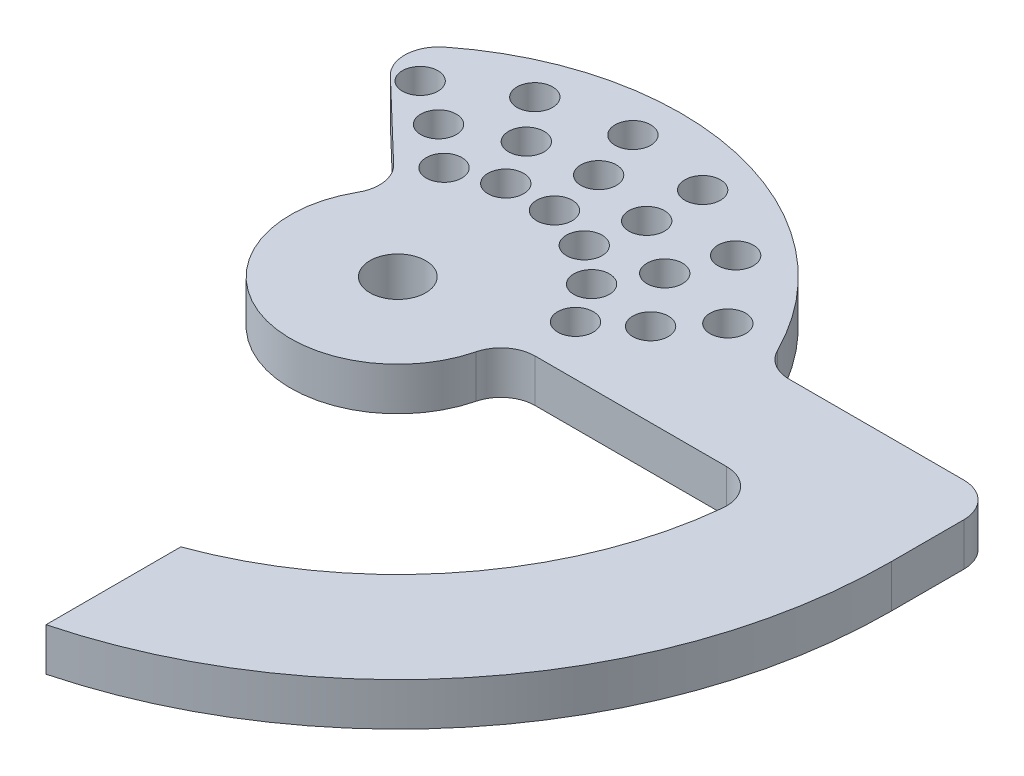
SolidWorks part; units mm, degrees
ref_plane "Front Plane" through (0, 0, 0) normal (0, 0, 1) x (1, 0, 0)
ref_plane "Top Plane" through (0, 0, 0) normal (0, 1, 0) x (1, 0, 0)
ref_plane "Right Plane" through (0, 0, 0) normal (1, 0, 0) x (0, 0, -1)
sketch "Sketch1" plane through (0, 0, 0) normal (0, 1, 0) x (1, 0, 0)
  circle A0 centre (0, 0) radius 12.5
  dimension "D1" = 25
extrude "Boss-Extrude1" add sketch "Sketch1" along normal blind 5
sketch "Sketch4" plane through (0, 0, 0) normal (0, 1, 0) x (1, 0, 0)
  line L0 (0, 0) -> (50, 0) construction
  line L1 (0, 0) -> (14.6186, -47.8152) construction
  arc A0 (14.6186, -47.8152) -> (50, 0) centre (0, 0) ccw
  dimension "D2" = 73
  dimension "D3" = 50
extrude "Extrude-Thin1" add sketch "Sketch4" along normal blind 5 separate body thin thin type mid plane wall 15
sketch "Sketch6" plane through (0, 0, 0) normal (0, 1, 0) x (1, 0, 0)
  line L1 (57.5, 0) -> (1, 0)
  line L2 (57.5, 0) -> (57.5, 12.4599)
  line L3 (57.5, 12.4599) -> (1, 12.4599)
  line L4 (1, 0) -> (1, 12.4599)
  line L5 (29.25, 12.4599) -> (29.25, 0) construction
  line L6 (57.5, 6.23) -> (1, 6.23) construction
  circle A0 centre (0, 0) radius 12.5 construction
  point P104 (29.25, 6.23)
extrude "Boss-Extrude3" add sketch "Sketch6" along normal up to surface (5 mm away) up to face at (0, 5, 12.5)
sketch "Sketch7" plane through (0, 5, 0) normal (0, 1, 0) x (1, 0, 0)
  circle A0 centre (0, 0) radius 3.25
  dimension "D1" = 6.5
extrude "Cut-Extrude3" cut sketch "Sketch7" against normal through all both and the other way through all
sketch "Sketch9" plane through (0, 0, 0) normal (0, 1, 0) x (1, 0, 0)
  line L0 (16.8114, -54.9875) -> (12.4258, -40.643) construction
  line L1 (0, 0) -> (23.9434, 0) construction
  line L2 (12.5, 0) -> (42.5, 0) construction
  line L3 (14.6186, 0) -> (14.6186, -61.8648) construction
  line L4 (12.4258, -40.643) -> (11.863, -56.263)
  line L5 (14.6186, -37.5897) -> (4.9921, -37.5897)
  line L6 (14.6186, -37.5897) -> (14.6186, -60.7122)
  line L7 (14.6186, -60.7122) -> (4.9921, -60.7122)
  line L8 (4.9921, -37.5897) -> (4.9921, -60.7122)
  line L9 (9.8053, -60.7122) -> (9.8053, -37.5897) construction
  line L10 (14.6186, -49.151) -> (4.9921, -49.151) construction
  line L11 (16.8114, -54.9875) -> (12.4258, -40.643)
  arc A0 (16.8114, -54.9875) -> (11.863, -56.263) centre (0, 0) cw
  point P0 (14.6186, -47.8152)
  point P166 (9.8053, -49.151)
extrude "Boss-Extrude4" add sketch "Sketch9" along normal blind 5 contours A0 L11 L6 | A0 L6 L11 L4 region at (13.2318, 0, 50.04) region at (15.3502, 0, 52.8095)
extrude "Cut-Extrude5" cut sketch "Sketch9<4>" along normal through all contours L6 L7 L8 L5
sketch "Sketch9<4>" plane through (0, 0, 0) normal (0, 1, 0) x (1, 0, 0) same geometry as "Sketch9"
sketch "Sketch10" plane through (0, 0, 0) normal (0, 1, 0) x (1, 0, 0)
  line L0 (0, 0) -> (-23.8274, 22.8311) construction
  line L4 (-23.8274, 22.8311) -> (-5.9312, 5.6832)
  line L6 (31.686, 9.2196) -> (0, 0) construction
  line L7 (31.686, 9.2196) -> (19.5321, 5.6832)
  line L8 (19.5321, 5.6832) -> (-5.9312, 5.6832)
  arc A0 (-23.8274, 22.8311) -> (31.686, 9.2196) centre (0, 0) cw
  point P5 (33.6063, 9.7783)
  point P7 (-24.9195, 24.5768)
  dimension "D1" = 33
  dimension "D2" = 120
extrude "Boss-Extrude5" add sketch "Sketch10" along normal up to surface (5 mm away) up to face at (28.5796, 5, 13.8571)
sketch "Sketch11" plane through (0, 5, 0) normal (0, 1, 0) x (1, 0, 0)
  line L0 (0, 0) -> (-17.1064, 28.2201) construction
  line L1 (-23.8274, 22.8311) -> (-9.0255, 8.6481) construction
  arc A0 (30.5573, 12.4599) -> (-23.8274, 22.8311) centre (0, 0) ccw construction
  circle A2 centre (-8.294, 13.6825) radius 2.075
  dimension "D2" = 4.15
  dimension "D4" = 16
  dimension "D5" = 15
extrude "Cut-Extrude6" cut sketch "Sketch11" against normal through all
sketch "Sketch12" plane through (0, 5, 0) normal (0, 1, 0) x (1, 0, 0)
  line L0 (0, 0) -> (-17.1064, 28.2201) construction
  line L1 (-23.8274, 22.8311) -> (-9.0255, 8.6481) construction
  line L2 (0, 0) -> (-19.5008, 26.6218) construction
  arc A0 (30.5573, 12.4599) -> (-23.8274, 22.8311) centre (0, 0) ccw construction
  circle A1 centre (-13.0005, 17.7478) radius 2.075
  point P11 (-9.4549, 12.9075)
  dimension "D3" = 6
  dimension "D4" = 4.15
  dimension "D1" = 15
  dimension "D2" = 16
  dimension "D5" = 5
extrude "Cut-Extrude7" cut sketch "Sketch12" against normal through all
sketch "Sketch13" plane through (0, 5, 0) normal (0, 1, 0) x (1, 0, 0)
  line L0 (0, 0) -> (-17.1064, 28.2201) construction
  line L1 (0, 0) -> (-21.7468, 24.8209) construction
  line L2 (-23.8274, 22.8311) -> (-9.0255, 8.6481) construction
  arc A0 (30.5573, 12.4599) -> (-23.8274, 22.8311) centre (0, 0) ccw construction
  circle A1 centre (-18.4519, 21.0601) radius 2.075
  point P9 (-14.4979, 16.5472)
  dimension "D3" = 4.15
  dimension "D5" = 6
  dimension "D1" = 15
  dimension "D2" = 10
  dimension "D4" = 22
extrude "Cut-Extrude8" cut sketch "Sketch13" against normal through all
pattern_circular "CirPattern1" count 6 every 20 about axis through (0, 5, 0) along (0, 1, 0) of "Cut-Extrude6" reverse direction yes
pattern_circular "CirPattern2" count 6 every 20 about axis through (0, 5, 0) along (0, 1, 0) of "Cut-Extrude7" reverse direction yes
pattern_circular "CirPattern3" count 6 every 20 about axis through (0, 5, 0) along (0, 1, 0) of "Cut-Extrude8" reverse direction yes
fillet "Fillet2" radius 4 6 edges at (12.5, 2.5, 0) (57.5, 2.5, -12.4599) (42.5, 2.5, 0) (30.5573, 2.5, -12.4599) (-23.8274, 2.5, -22.8311) (-9.0255, 2.5, -8.6481)
